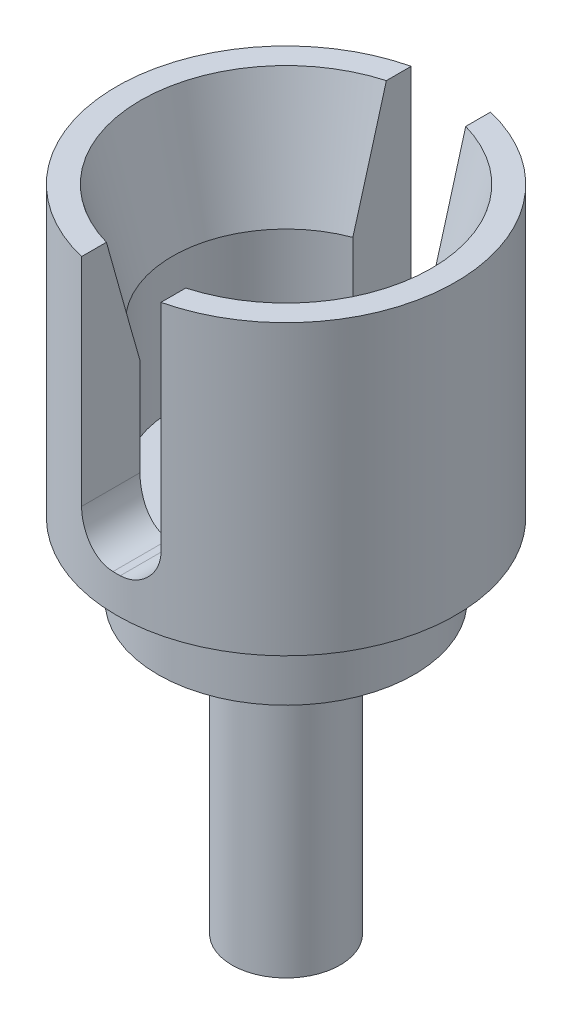
SolidWorks part; units mm, degrees
ref_plane "Front Plane" through (0, 0, 0) normal (0, 0, 1) x (1, 0, 0)
ref_plane "Top Plane" through (0, 0, 0) normal (0, 1, 0) x (1, 0, 0)
ref_plane "Right Plane" through (0, 0, 0) normal (1, 0, 0) x (0, 0, -1)
sketch "Sketch1" plane through (0, 0, 0) normal (0, 1, 0) x (1, 0, 0)
  circle A0 centre (0, 0) radius 1.5
  circle A1 centre (0, 0) radius 3.55
  dimension "D1" = 3
  dimension "D2" = 7.1
extrude "Boss-Extrude1" add sketch "Sketch1" against normal blind 8 contours A0
extrude "Boss-Extrude2" add sketch "Sketch1<3>" along normal blind 2 contours A0 | A1 A0 region at (0, 0, 0) region at (-3.4496, 0, 0)
sketch "Sketch1<3>" plane through (0, 0, 0) normal (0, 1, 0) x (1, 0, 0) same geometry as "Sketch1"
sketch "Sketch2" plane through (0, 2, 0) normal (0, 1, 0) x (1, 0, 0)
  circle A0 centre (0, 0) radius 4.7
  dimension "D1" = 9.4
extrude "Boss-Extrude3" add sketch "Sketch2" along normal blind 8
sketch "Sketch3" plane through (0, 10, 0) normal (0, 1, 0) x (1, 0, 0)
  circle A0 centre (0, 0) radius 3.15
  dimension "D1" = 6.3
extrude "Cut-Extrude1" cut sketch "Sketch3" against normal blind 7 and the other way through all
chamfer "Chamfer1" distance 3.3 angle 15 1 edges at (0, 10, 3.15) first distance on face at (0, 10, 3.15)
sketch "Sketch4" plane through (0, 0, 0) normal (0, 0, 1) x (1, 0, 0)
  line L0 (-4.7, 10) -> (-4.7, 2) construction
  line L1 (-1.1, 10) -> (1.1, 10)
  line L2 (-1.1, 10) -> (-1.1, 3)
  line L3 (-1.1, 3) -> (1.1, 3)
  line L4 (1.1, 10) -> (1.1, 3)
  line L5 (-1.1, 10) -> (1.1, 3) construction
  line L6 (-1.1, 3) -> (1.1, 10) construction
  line L7 (4.0342, 10) -> (-4.0342, 10) construction
  point P0 (0, 6.5)
  point P5 (-0.1518, 6.8626)
  dimension "D1" = 4.7
  dimension "D2" = 2.2
  dimension "D3" = 7
extrude "Cut-Extrude2" cut sketch "Sketch4" against normal through all both and the other way through all
fillet "Fillet1" radius 1 4 edges at (1.1, 3, -3.7606) (-1.1, 3, -3.7606) (1.1, 3, 3.7606) (-1.1, 3, 3.7606)
